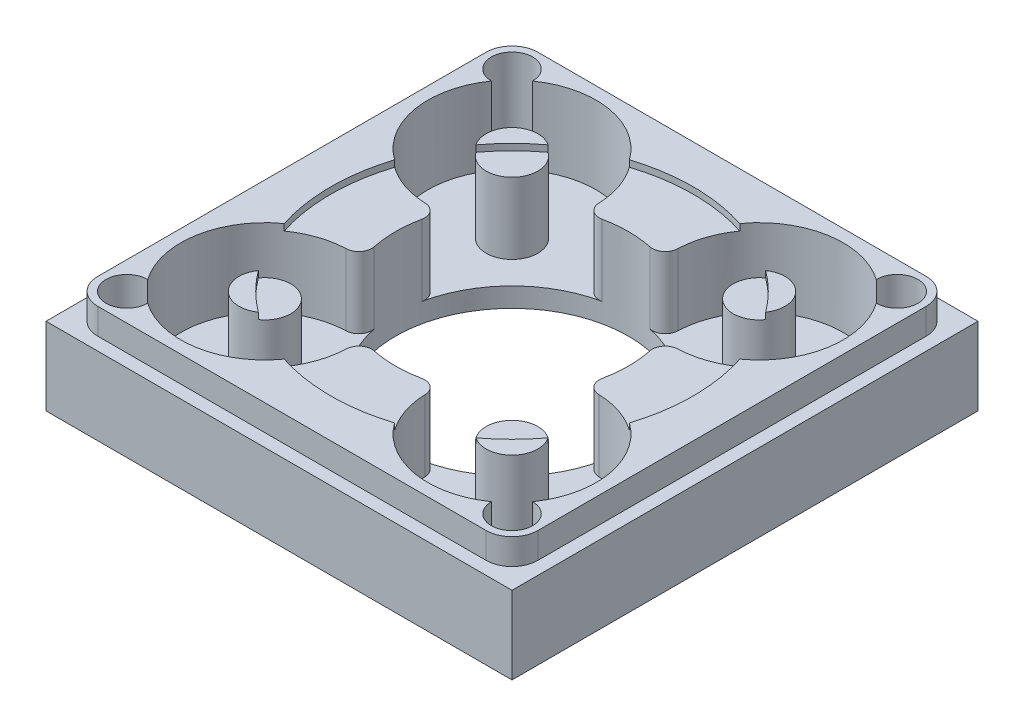
SolidWorks part; units mm, degrees
material "6061 Alloy"
ref_plane "Front Plane" through (0, 0, 0) normal (0, 0, 1) x (1, 0, 0)
ref_plane "Top Plane" through (0, 0, 0) normal (0, 1, 0) x (1, 0, 0)
ref_plane "Right Plane" through (0, 0, 0) normal (1, 0, 0) x (0, 0, -1)
sketch "Sketch1" plane through (0, 0, 0) normal (0, 1, 0) x (1, 0, 0)
  line L1 (-28.575, -28.575) -> (28.575, -28.575)
  line L2 (-28.575, -28.575) -> (-28.575, 28.575)
  line L3 (-28.575, 28.575) -> (28.575, 28.575)
  line L4 (28.575, -28.575) -> (28.575, 28.575)
  line L5 (-28.575, -28.575) -> (28.575, 28.575) construction
  line L6 (-28.575, 28.575) -> (28.575, -28.575) construction
  circle A0 centre (0, 0) radius 14.2875
  point P0 (0, 0)
  dimension "D2" = 28.575
  dimension "D1" = 57.15
extrude "Boss-Extrude1" add sketch "Sketch1" along normal blind 12.7
sketch "Sketch2" plane through (0, 12.7, 0) normal (0, 1, 0) x (1, 0, 0)
  line L1 (-23.8125, -26.9875) -> (23.8125, -26.9875)
  line L2 (-26.9875, -23.8125) -> (-26.9875, 23.8125)
  line L3 (-23.8125, 26.9875) -> (23.8125, 26.9875)
  line L4 (26.9875, -23.8125) -> (26.9875, 23.8125)
  line L5 (-26.9875, -26.9875) -> (26.9875, 26.9875) construction
  line L6 (-26.9875, 26.9875) -> (26.9875, -26.9875) construction
  line L7 (28.575, 28.575) -> (-28.575, 28.575)
  line L8 (28.575, 28.575) -> (28.575, -28.575)
  line L9 (28.575, -28.575) -> (-28.575, -28.575)
  line L10 (-28.575, 28.575) -> (-28.575, -28.575)
  line L11 (28.575, 28.575) -> (-28.575, -28.575) construction
  line L12 (28.575, -28.575) -> (-28.575, 28.575) construction
  arc A0 (23.8125, 26.9875) -> (26.9875, 23.8125) centre (23.8125, 23.8125) cw
  arc A1 (23.8125, -26.9875) -> (26.9875, -23.8125) centre (23.8125, -23.8125) ccw
  arc A2 (-23.8125, -26.9875) -> (-26.9875, -23.8125) centre (-23.8125, -23.8125) cw
  arc A3 (-26.9875, 23.8125) -> (-23.8125, 26.9875) centre (-23.8125, 23.8125) cw
  point P0 (0, 0)
  point P18 (0, 0)
  dimension "D2" = 3.175
  dimension "D1" = 53.975
extrude "Cut-Extrude1" cut sketch "Sketch2" against normal blind 3.175
sketch "Sketch4" plane through (0, 12.7, 0) normal (0, 1, 0) x (1, 0, 0)
  line L0 (0, 0) -> (15.1542, 15.1542) construction
  line L1 (28.575, -28.575) -> (28.575, 28.575) construction
  circle A0 centre (15.1542, 15.1542) radius 10.3187
  circle A1 centre (15.1542, -15.1542) radius 10.3187
  circle A2 centre (-15.1542, -15.1542) radius 10.3188
  circle A3 centre (-15.1542, 15.1542) radius 10.3188
  circle A4 centre (15.1542, 15.1542) radius 3.175
  circle A5 centre (15.1542, -15.1542) radius 3.175
  circle A6 centre (-15.1542, -15.1542) radius 3.175
  circle A7 centre (-15.1542, 15.1542) radius 3.175
  point P15 (0, 0)
  point P23 (0, 0)
  dimension "D3" = 20.6375
  dimension "D5" = 6.35
  dimension "D1" = 21.4312
  dimension "D2" = 45
  dimension "D4" = 4
  dimension "D6" = 4
extrude "Cut-Extrude3" cut sketch "Sketch4" against normal blind 9.525
sketch "Sketch5" plane through (0, 12.7, 0) normal (0, 1, 0) x (1, 0, 0)
  circle A0 centre (0, 0) radius 22.225
  dimension "D1" = 44.45
extrude "Cut-Extrude4" cut sketch "Sketch5" against normal blind 0.7937
sketch "Sketch6" plane through (0, 0, 0) normal (0, -1, 0) x (1, 0, 0)
  line L1 (23.622, -23.622) -> (-23.622, -23.622) construction
  line L2 (23.622, -23.622) -> (23.622, 23.622) construction
  line L3 (23.622, 23.622) -> (-23.622, 23.622) construction
  line L4 (-23.622, -23.622) -> (-23.622, 23.622) construction
  line L5 (23.622, -23.622) -> (-23.622, 23.622) construction
  line L6 (23.622, 23.622) -> (-23.622, -23.622) construction
  circle A0 centre (-23.622, 23.622) radius 2.54
  circle A1 centre (23.622, 23.622) radius 2.54
  circle A2 centre (23.622, -23.622) radius 2.54
  circle A3 centre (-23.622, -23.622) radius 2.54
  point P0 (0, 0)
  dimension "D2" = 5.08
  dimension "D1" = 47.244
extrude "Cut-Extrude5" cut sketch "Sketch6" against normal through all
sketch "Sketch8" plane through (0, 0, 0) normal (0, -1, 0) x (1, 0, 0)
  circle A0 centre (0, 0) radius 22.225
  dimension "D1" = 44.45
extrude "Cut-Extrude6" cut sketch "Sketch8" against normal blind 0.7937
fillet "Fillet1" radius 1.5875 8 edges at (4.9876, 7.5406, -13.3887) (-4.9876, 7.5406, -13.3887) (-13.3887, 7.5406, -4.9876) (-13.3887, 7.5406, 4.9876) (-4.9876, 7.5406, 13.3887) (4.9876, 7.5406, 13.3887) (13.3887, 7.5406, 4.9876) (13.3887, 7.5406, -4.9876)
